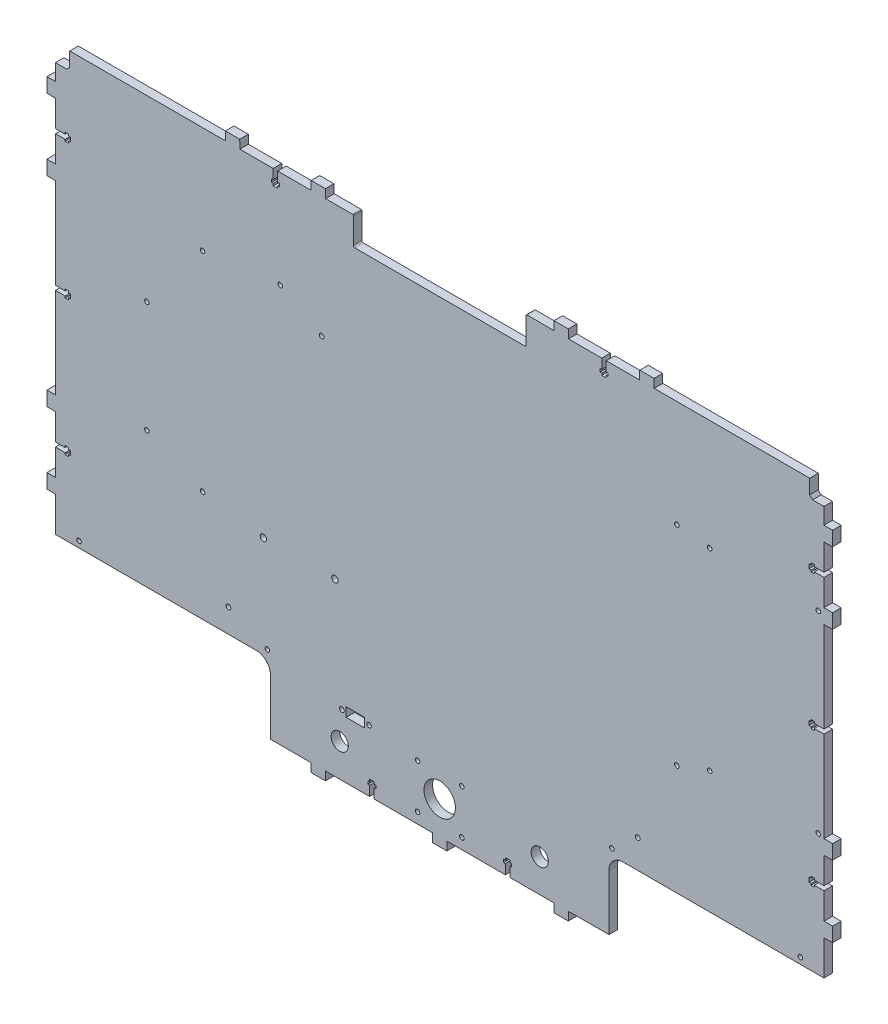
SolidWorks part; units mm, degrees
material "Клен"
ref_plane "Front" through (0, 0, 0) normal (0, 0, 1) x (1, 0, 0)
ref_plane "Top" through (0, 0, 0) normal (0, 1, 0) x (1, 0, 0)
ref_plane "Right" through (0, 0, 0) normal (1, 0, 0) x (0, 0, -1)
sketch "Эскиз1" plane through (0, 0, 0) normal (0, 0, 1) x (1, 0, 0)
  line L0 (89.7419, 500.1376) -> (118.0919, 500.1376)
  line L1 (118.0919, 500.1376) -> (118.1919, 494.1376)
  line L2 (118.1919, 494.1376) -> (128.1919, 494.1376)
  line L3 (128.1919, 494.1376) -> (128.2919, 500.1376)
  line L4 (128.2919, 500.1376) -> (159.1419, 500.1376)
  line L5 (159.1419, 500.1376) -> (159.1419, 506.9376)
  line L6 (159.1419, 506.9376) -> (157.9419, 506.9376)
  line L7 (157.9419, 506.9376) -> (157.9419, 509.1376)
  line L8 (157.9419, 509.1376) -> (159.1419, 509.1376)
  line L9 (159.1419, 509.1376) -> (159.1419, 510.6376)
  line L10 (159.1419, 510.6376) -> (162.2419, 510.6376)
  line L11 (162.2419, 510.6376) -> (162.2419, 509.1376)
  line L12 (162.2419, 509.1376) -> (163.4419, 509.1376)
  line L13 (163.4419, 509.1376) -> (163.4419, 506.9376)
  line L14 (163.4419, 506.9376) -> (162.2419, 506.9376)
  line L15 (162.2419, 506.9376) -> (162.2419, 500.1376)
  line L16 (-51.8081, 695.792) -> (-54.0081, 695.792)
  line L17 (-66.8081, 623.542) -> (-60.8081, 623.442)
  line L18 (162.2419, 500.1376) -> (203.0919, 500.1376)
  line L19 (203.0919, 500.1376) -> (203.1919, 494.1376)
  line L20 (203.1919, 494.1376) -> (213.1919, 494.1376)
  line L21 (213.1919, 494.1376) -> (213.2919, 500.1376)
  line L22 (213.2919, 500.1376) -> (254.1419, 500.1376)
  line L23 (254.1419, 500.1376) -> (254.1419, 506.9376)
  line L24 (254.1419, 506.9376) -> (252.9419, 506.9376)
  line L25 (252.9419, 506.9376) -> (252.9419, 509.1376)
  line L26 (252.9419, 509.1376) -> (254.1419, 509.1376)
  line L27 (254.1419, 509.1376) -> (254.1419, 510.6376)
  line L28 (254.1419, 510.6376) -> (257.2419, 510.6376)
  line L29 (257.2419, 510.6376) -> (257.2419, 509.1376)
  line L30 (257.2419, 509.1376) -> (258.4419, 509.1376)
  line L31 (258.4419, 509.1376) -> (258.4419, 506.9376)
  line L32 (258.4419, 506.9376) -> (257.2419, 506.9376)
  line L33 (257.2419, 506.9376) -> (257.2419, 500.1376)
  line L34 (257.2419, 500.1376) -> (288.0919, 500.1376)
  line L35 (288.0919, 500.1376) -> (288.1919, 494.1376)
  line L36 (288.1919, 494.1376) -> (298.1919, 494.1376)
  line L37 (298.1919, 494.1376) -> (298.2919, 500.1376)
  line L38 (298.2919, 500.1376) -> (326.6419, 500.1376)
  line L97 (367.1919, 847.1376) -> (358.2919, 847.1376)
  line L98 (358.2919, 847.1376) -> (358.1919, 853.1376)
  line L99 (358.1919, 853.1376) -> (348.1919, 853.1376)
  line L100 (348.1919, 853.1376) -> (348.0919, 847.1376)
  line L101 (348.0919, 847.1376) -> (324.7419, 847.1376)
  line L102 (324.7419, 847.1376) -> (324.7419, 840.3376)
  line L103 (324.7419, 840.3376) -> (325.9419, 840.3376)
  line L104 (325.9419, 840.3376) -> (325.9419, 838.1376)
  line L105 (325.9419, 838.1376) -> (324.7419, 838.1376)
  line L106 (324.7419, 838.1376) -> (324.7419, 836.6376)
  line L107 (324.7419, 836.6376) -> (321.6419, 836.6376)
  line L108 (321.6419, 836.6376) -> (321.6419, 838.1376)
  line L109 (321.6419, 838.1376) -> (320.4419, 838.1376)
  line L110 (320.4419, 838.1376) -> (320.4419, 840.3376)
  line L111 (320.4419, 840.3376) -> (321.6419, 840.3376)
  line L112 (321.6419, 840.3376) -> (321.6419, 847.1376)
  line L113 (321.6419, 847.1376) -> (298.2919, 847.1376)
  line L114 (298.2919, 847.1376) -> (298.1919, 853.1376)
  line L115 (298.1919, 853.1376) -> (288.1919, 853.1376)
  line L116 (288.1919, 853.1376) -> (288.0919, 847.1376)
  line L117 (288.0919, 847.1376) -> (269.1919, 847.1376)
  line L118 (268.6919, 846.6376) -> (268.6919, 828.542)
  line L119 (267.6919, 827.542) -> (148.6919, 827.542)
  line L120 (147.6919, 828.542) -> (147.6919, 846.542)
  line L130 (94.7419, 838.042) -> (94.7419, 836.542)
  line L131 (94.7419, 836.542) -> (91.6419, 836.542)
  line L132 (91.6419, 836.542) -> (91.6419, 838.042)
  line L199 (39.1919, 871.432) -> (39.1919, 501.6876) construction
  line L201 (142.7002, 546.3976) -> (155.7002, 546.3976)
  line L202 (155.7002, 546.3976) -> (155.7002, 539.8976)
  line L203 (155.7002, 539.8976) -> (142.7002, 539.8976)
  line L204 (142.7002, 539.8976) -> (142.7002, 546.3976)
  line L205 (-60.8081, 871.432) -> (-60.8081, 501.6876) construction
  line L206 (-50.3081, 791.992) -> (-51.8081, 791.992)
  line L207 (-60.8081, 696.992) -> (-60.8081, 633.642)
  line L208 (-60.8081, 795.092) -> (-54.0081, 795.092)
  line L209 (-51.8081, 791.992) -> (-51.8081, 790.792)
  line L210 (-54.0081, 700.092) -> (-54.0081, 701.292)
  line L211 (-51.8081, 700.092) -> (-50.3081, 700.092)
  line L212 (-60.8081, 835.042) -> (-60.8081, 823.642)
  line L213 (-51.8081, 795.092) -> (-50.3081, 795.092)
  line L214 (-54.0081, 701.292) -> (-51.8081, 701.292)
  line L215 (-50.3081, 696.992) -> (-51.8081, 696.992)
  line L216 (-54.0081, 601.992) -> (-60.8081, 601.992)
  line L217 (-60.8081, 773.642) -> (-66.8081, 773.542)
  line L218 (-50.3081, 601.992) -> (-51.8081, 601.992)
  line L219 (-60.8081, 813.442) -> (-60.8081, 795.092)
  line L220 (-54.0081, 795.092) -> (-54.0081, 796.292)
  line L221 (-54.0081, 796.292) -> (-51.8081, 796.292)
  line L222 (-51.8081, 696.992) -> (-51.8081, 695.792)
  line L223 (-54.0081, 606.292) -> (-51.8081, 606.292)
  line L224 (-60.8081, 573.442) -> (-60.8081, 549.042)
  line L225 (-52.8081, 835.042) -> (-60.8081, 835.042)
  line L226 (-54.0081, 790.792) -> (-54.0081, 791.992)
  line L227 (-51.8081, 605.092) -> (-50.3081, 605.092)
  line L228 (-66.8081, 583.542) -> (-66.8081, 573.542)
  line L229 (-51.8081, 790.792) -> (-54.0081, 790.792)
  line L230 (-54.0081, 605.092) -> (-54.0081, 606.292)
  line L231 (-51.8081, 601.992) -> (-51.8081, 600.792)
  line L232 (-66.8081, 823.542) -> (-66.8081, 813.542)
  line L233 (-50.3081, 795.092) -> (-50.3081, 791.992)
  line L234 (-60.8081, 633.642) -> (-66.8081, 633.542)
  line L235 (-60.8081, 583.642) -> (-66.8081, 583.542)
  line L236 (-66.8081, 813.542) -> (-60.8081, 813.442)
  line L237 (-66.8081, 773.542) -> (-66.8081, 763.542)
  line L238 (-51.8081, 600.792) -> (-54.0081, 600.792)
  line L239 (-66.8081, 763.542) -> (-60.8081, 763.442)
  line L240 (-50.3081, 700.092) -> (-50.3081, 696.992)
  line L241 (-60.8081, 623.442) -> (-60.8081, 605.092)
  line L243 (-54.0081, 791.992) -> (-60.8081, 791.992)
  line L244 (-54.0081, 695.792) -> (-54.0081, 696.992)
  line L245 (-60.8081, 823.642) -> (-66.8081, 823.542)
  line L246 (-51.8081, 796.292) -> (-51.8081, 795.092)
  line L247 (-51.8081, 701.292) -> (-51.8081, 700.092)
  line L248 (-60.8081, 601.992) -> (-60.8081, 583.642)
  line L249 (-54.0081, 696.992) -> (-60.8081, 696.992)
  line L250 (-66.8081, 633.542) -> (-66.8081, 623.542)
  line L251 (-60.8081, 763.442) -> (-60.8081, 700.092)
  line L252 (-54.0081, 600.792) -> (-54.0081, 601.992)
  line L254 (-50.8081, 847.042) -> (-50.8081, 837.042)
  line L255 (-50.8081, 837.042) -> (-52.8081, 835.042)
  line L256 (-60.8081, 700.092) -> (-54.0081, 700.092)
  line L257 (-60.8081, 605.092) -> (-54.0081, 605.092)
  line L258 (-50.3081, 605.092) -> (-50.3081, 601.992)
  line L259 (-60.8081, 791.992) -> (-60.8081, 773.642)
  line L260 (-51.8081, 606.292) -> (-51.8081, 605.092)
  line L261 (-66.8081, 573.542) -> (-60.8081, 573.442)
  line L264 (377.1919, 871.432) -> (377.1919, 476.2445) construction
  line L265 (477.1919, 835.042) -> (477.1919, 823.642)
  line L325 (367.1919, 847.1376) -> (467.1919, 847.1376)
  line L326 (336.6419, 549.1376) -> (377.1919, 549.1376)
  line L327 (326.6419, 500.1376) -> (326.6419, 539.1376)
  line L328 (377.1919, 549.1376) -> (477.1919, 549.1376)
  line L329 (89.7419, 539.042) -> (89.7419, 500.1376)
  line L330 (79.7419, 549.042) -> (39.1919, 549.042)
  line L331 (-60.8081, 549.042) -> (39.1919, 549.042)
  line L332 (208.1919, 486.1481) -> (208.1919, 880.8098) construction
  line L333 (107.749, 553.442) -> (-66.0548, 553.442) construction
  line L334 (315.5919, 553.5376) -> (489.3697, 553.5376) construction
  line L335 (87.5419, 557.9345) -> (87.5419, 540.5243) construction
  line L336 (328.7419, 492.2341) -> (328.7419, 562.4741) construction
  line L337 (42.1919, 871.432) -> (42.1919, 565.6434) construction
  line L338 (-84.499, 772.492) -> (54.9834, 772.492) construction
  line L339 (-84.499, 626.492) -> (54.9834, 626.492) construction
  line L340 (94.7419, 840.3376) -> (94.7419, 847.1376)
  line L341 (95.9419, 840.3376) -> (94.7419, 840.3376)
  line L342 (95.9419, 838.1376) -> (95.9419, 840.3376)
  line L343 (94.7419, 838.1376) -> (95.9419, 838.1376)
  line L344 (94.7419, 836.6376) -> (94.7419, 838.1376)
  line L345 (91.6419, 836.6376) -> (94.7419, 836.6376)
  line L346 (91.6419, 838.1376) -> (91.6419, 836.6376)
  line L347 (90.4419, 838.1376) -> (91.6419, 838.1376)
  line L348 (90.4419, 840.3376) -> (90.4419, 838.1376)
  line L349 (91.6419, 840.3376) -> (90.4419, 840.3376)
  line L350 (91.6419, 847.1376) -> (91.6419, 840.3376)
  line L351 (49.1919, 847.1376) -> (-50.8081, 847.1376)
  line L352 (128.2919, 847.1376) -> (147.1919, 847.1376)
  line L353 (128.1919, 853.1376) -> (128.2919, 847.1376)
  line L354 (118.1919, 853.1376) -> (128.1919, 853.1376)
  line L355 (118.0919, 847.1376) -> (118.1919, 853.1376)
  line L356 (94.7419, 847.1376) -> (118.0919, 847.1376)
  line L357 (68.2919, 847.1376) -> (91.6419, 847.1376)
  line L358 (68.1919, 853.1376) -> (68.2919, 847.1376)
  line L359 (58.1919, 853.1376) -> (68.1919, 853.1376)
  line L360 (58.0919, 847.1376) -> (58.1919, 853.1376)
  line L361 (49.1919, 847.1376) -> (58.0919, 847.1376)
  line L362 (147.6919, 846.6376) -> (147.6919, 846.542)
  line L363 (-50.8081, 847.1376) -> (-50.8081, 847.042)
  line L364 (467.1919, 847.1376) -> (467.1919, 847.042)
  line L365 (467.1919, 837.042) -> (469.1919, 835.042)
  line L366 (467.1919, 847.042) -> (467.1919, 837.042)
  line L367 (469.1919, 835.042) -> (477.1919, 835.042)
  line L368 (477.1919, 791.992) -> (477.1919, 773.642)
  line L369 (468.1919, 796.292) -> (468.1919, 795.092)
  line L370 (477.1919, 823.642) -> (483.1919, 823.542)
  line L371 (470.3919, 791.992) -> (477.1919, 791.992)
  line L372 (483.1919, 813.542) -> (477.1919, 813.442)
  line L373 (466.6919, 795.092) -> (466.6919, 791.992)
  line L374 (483.1919, 823.542) -> (483.1919, 813.542)
  line L375 (468.1919, 790.792) -> (470.3919, 790.792)
  line L376 (470.3919, 790.792) -> (470.3919, 791.992)
  line L377 (470.3919, 796.292) -> (468.1919, 796.292)
  line L378 (470.3919, 795.092) -> (470.3919, 796.292)
  line L379 (477.1919, 813.442) -> (477.1919, 795.092)
  line L380 (468.1919, 795.092) -> (466.6919, 795.092)
  line L381 (468.1919, 791.992) -> (468.1919, 790.792)
  line L382 (477.1919, 795.092) -> (470.3919, 795.092)
  line L383 (466.6919, 791.992) -> (468.1919, 791.992)
  line L384 (483.1919, 763.542) -> (477.1919, 763.442)
  line L385 (483.1919, 773.542) -> (483.1919, 763.542)
  line L386 (477.1919, 773.642) -> (483.1919, 773.542)
  line L387 (477.1919, 763.442) -> (477.1919, 700.092)
  line L388 (477.1919, 700.092) -> (470.3919, 700.092)
  line L389 (470.3919, 696.992) -> (477.1919, 696.992)
  line L390 (468.1919, 701.292) -> (468.1919, 700.092)
  line L391 (470.3919, 695.792) -> (470.3919, 696.992)
  line L392 (466.6919, 700.092) -> (466.6919, 696.992)
  line L393 (468.1919, 696.992) -> (468.1919, 695.792)
  line L394 (466.6919, 696.992) -> (468.1919, 696.992)
  line L395 (470.3919, 701.292) -> (468.1919, 701.292)
  line L396 (468.1919, 700.092) -> (466.6919, 700.092)
  line L397 (470.3919, 700.092) -> (470.3919, 701.292)
  line L398 (468.1919, 695.792) -> (470.3919, 695.792)
  line L399 (477.1919, 696.992) -> (477.1919, 633.642)
  line L400 (477.1919, 601.992) -> (477.1919, 583.642)
  line L401 (468.1919, 606.292) -> (468.1919, 605.092)
  line L402 (466.6919, 605.092) -> (466.6919, 601.992)
  line L403 (477.1919, 605.092) -> (470.3919, 605.092)
  line L404 (470.3919, 600.792) -> (470.3919, 601.992)
  line L405 (483.1919, 633.542) -> (483.1919, 623.542)
  line L406 (477.1919, 623.442) -> (477.1919, 605.092)
  line L407 (468.1919, 600.792) -> (470.3919, 600.792)
  line L408 (477.1919, 633.642) -> (483.1919, 633.542)
  line L409 (468.1919, 601.992) -> (468.1919, 600.792)
  line L410 (470.3919, 605.092) -> (470.3919, 606.292)
  line L411 (468.1919, 605.092) -> (466.6919, 605.092)
  line L412 (470.3919, 606.292) -> (468.1919, 606.292)
  line L413 (466.6919, 601.992) -> (468.1919, 601.992)
  line L414 (470.3919, 601.992) -> (477.1919, 601.992)
  line L415 (483.1919, 623.542) -> (477.1919, 623.442)
  line L416 (483.1919, 573.542) -> (477.1919, 573.442)
  line L417 (477.1919, 583.642) -> (483.1919, 583.542)
  line L418 (483.1919, 583.542) -> (483.1919, 573.542)
  line L419 (477.1919, 573.442) -> (477.1919, 549.042)
  circle A0 centre (138.1919, 523.1376) radius 6
  circle A1 centre (208.1919, 523.1376) radius 11
  circle A2 centre (278.1919, 523.1376) radius 6
  circle A3 centre (192.6919, 538.6376) radius 1.6
  circle A4 centre (223.6919, 538.6376) radius 1.6
  circle A5 centre (158.7002, 543.1376) radius 1.6265
  circle A6 centre (139.7002, 543.1376) radius 1.7
  circle A7 centre (192.6919, 507.6376) radius 1.6
  circle A8 centre (223.6919, 507.6376) radius 1.6
  circle A18 centre (84.7857, 619.7888) radius 2.25
  circle A19 centre (134.7857, 619.7888) radius 2.25
  circle A24 centre (346.7847, 569.0716) radius 1.7
  circle A26 centre (60.3069, 565.6434) radius 1.7
  arc A30 (148.6919, 827.542) -> (147.6919, 828.542) centre (148.6919, 828.542) cw
  arc A31 (268.6919, 828.542) -> (267.6919, 827.542) centre (267.6919, 828.542) cw
  arc A32 (269.1919, 847.1376) -> (268.6919, 846.6376) centre (269.1919, 846.6376) ccw
  arc A38 (326.6419, 539.1376) -> (336.6419, 549.1376) centre (336.6419, 539.1376) cw
  arc A39 (89.7419, 539.042) -> (79.7419, 549.042) centre (79.7419, 539.042) ccw
  circle A40 centre (-44.2581, 553.442) radius 1.6
  circle A41 centre (460.6419, 553.5376) radius 1.6
  circle A46 centre (87.5419, 553.442) radius 1.6
  circle A47 centre (328.7419, 553.5376) radius 1.6
  circle A48 centre (42.1919, 772.492) radius 1.6
  circle A49 centre (42.1919, 626.492) radius 1.6
  circle A50 centre (374.1919, 626.492) radius 1.6
  circle A51 centre (374.1919, 772.492) radius 1.6
  circle A52 centre (397.1919, 769.7505) radius 1.6
  circle A53 centre (473.1919, 769.7505) radius 1.6
  circle A54 centre (473.1919, 634.7505) radius 1.6
  circle A55 centre (397.1919, 634.7505) radius 1.6
  arc A56 (147.1919, 847.1376) -> (147.6919, 846.6376) centre (147.1919, 846.6376) cw
  circle A57 centre (96.5604, 778.9111) radius 1.6
  circle A58 centre (125.5604, 762.4937) radius 1.6
  circle A59 centre (3.1919, 722.1376) radius 1.6
  circle A60 centre (3.1919, 644.1376) radius 1.6
  dimension "D1" = 12
  dimension "D2" = 22
  dimension "D3" = 12
  dimension "D4" = 169
  dimension "D5" = 1
  dimension "D6" = 0.5
  dimension "D10" = 3.2
  dimension "D12" = 3.2
  dimension "D13" = 4.4
  dimension "D14" = 48.35
  dimension "D15" = 3.2
  dimension "D17" = 3.2
  dimension "D21" = 3.2
  dimension "D22" = 3.2
  dimension "D24" = 23
  dimension "D26" = 31
  dimension "D27" = 31
  dimension "D28" = 31
  dimension "D30" = 23
  dimension "D32" = 43
  dimension "D33" = 43
  dimension "D34" = 3.2
  dimension "D35" = 3.2
  dimension "D36" = 3.2
  dimension "D37" = 3.2
  dimension "D19" = 3.2
  dimension "D38" = 3.2
  dimension "D39" = 3.2
  dimension "D7" = 100
  dimension "D8" = 4.4
  dimension "D9" = 169
  dimension "D11" = 16.55
  dimension "D16" = 48.45
  dimension "D18" = 3
  dimension "D20" = 146
  dimension "D23" = 23
  dimension "D25" = 7.5
  dimension "D29" = 7.5
  dimension "D31" = 39.76
extrude "Бобышка-Вытянуть1" add sketch "Эскиз1" along normal blind 6 contours L0 L1 L2 L3 L4 L5 L6 L7 L8 L9 L10 L11 L12 L13 L14 L15 L18 L19 L20 L21 L22 L23 L24 L25 L26 L27 L28 L29 L30 L31 L32 L33 L34 L35 L36 L37 L38 region at (208.2158, 684.8431, 0)
